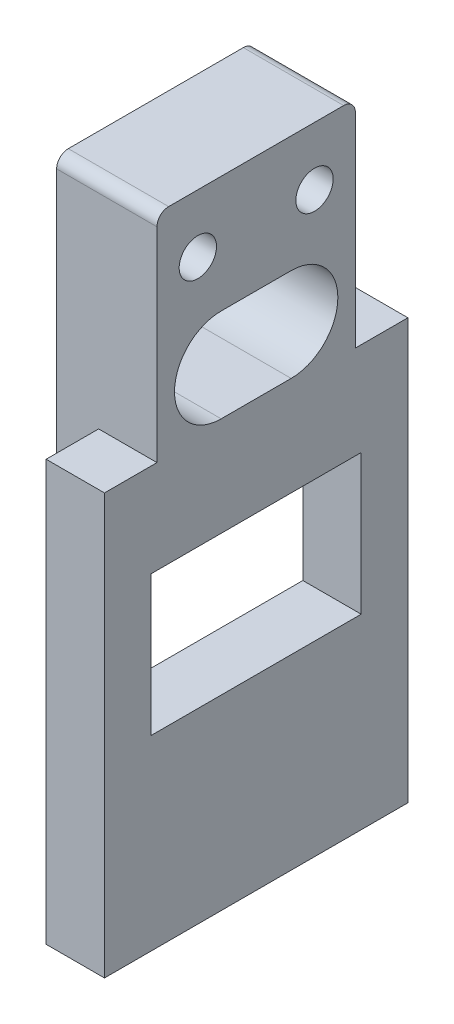
SolidWorks part; units mm, degrees
note: The reader was unsure of these and kept them because the rebuilt part matched: shared geometry of "Sketch2<3>", "Sketch2<7>".
material "ABS"
ref_plane "Front Plane" through (0, 0, 0) normal (0, 0, 1) x (1, 0, 0)
ref_plane "Top Plane" through (0, 0, 0) normal (0, 1, 0) x (1, 0, 0)
ref_plane "Right Plane" through (0, 0, 0) normal (1, 0, 0) x (0, 0, -1)
sketch "Sketch2" plane through (0, 0, 0) normal (1, 0, 0) x (0, 0, -1)
  line L0 (9, 19.5) -> (-9, 19.5) construction
  line L1 (-9, 19.5) -> (-9, 7.5) construction
  line L2 (9, 7.5) -> (-9, 7.5) construction
  line L3 (9, 19.5) -> (9, 7.5) construction
  line L4 (-11, 20.5) -> (11, 20.5) construction
  line L5 (11, 20.5) -> (11, -7.5) construction
  line L6 (11, -7.5) -> (-11, -7.5) construction
  line L7 (-11, -7.5) -> (-11, 20.5) construction
  line L8 (-3, 28) -> (3, 28) construction
  line L9 (-3, 36) -> (3, 36) construction
  line L10 (8.5, 22.5) -> (-8.5, 22.5) construction
  line L11 (8.5, 27.5) -> (-8.5, 27.5) construction
  line L12 (8.5, 46) -> (8.5, 22.5) construction
  line L13 (8.5, 22.5) -> (13, 22.5) construction
  line L14 (13, 22.5) -> (13, -8.5) construction
  line L15 (13, -8.5) -> (-13, -8.5) construction
  line L16 (-13, -8.5) -> (-13, 22.5) construction
  line L17 (-13, 22.5) -> (-8.5, 22.5) construction
  line L18 (-8.5, 22.5) -> (-8.5, 46) construction
  line L19 (-8.5, 46) -> (8.5, 46) construction
  line L20 (9, 19.5) -> (-9, 19.5)
  line L21 (-9, 19.5) -> (-9, 7.5)
  line L22 (9, 7.5) -> (-9, 7.5)
  line L23 (9, 19.5) -> (9, 7.5)
  line L24 (-11, 20.5) -> (11, 20.5)
  line L25 (11, 20.5) -> (11, -7.5)
  line L26 (11, -7.5) -> (-11, -7.5)
  line L27 (-11, -7.5) -> (-11, 20.5)
  line L28 (-3, 28) -> (3, 28)
  line L29 (-3, 36) -> (3, 36)
  line L30 (8.5, 22.5) -> (-8.5, 22.5)
  line L31 (8.5, 27.5) -> (-8.5, 27.5)
  line L32 (8.5, 46) -> (8.5, 22.5)
  line L33 (8.5, 22.5) -> (13, 22.5)
  line L34 (13, 22.5) -> (13, -8.5)
  line L35 (13, -8.5) -> (-13, -8.5)
  line L36 (-13, -8.5) -> (-13, 22.5)
  line L37 (-13, 22.5) -> (-8.5, 22.5)
  line L38 (-8.5, 22.5) -> (-8.5, 46)
  line L39 (-8.5, 46) -> (8.5, 46)
  line L40 (-13, 27.5) -> (-13, 22.5) construction
  line L41 (-8.5, 27.5) -> (-13, 27.5) construction
  line L42 (13, 22.5) -> (13, 27.5) construction
  line L43 (13, 27.5) -> (8.5, 27.5) construction
  line L44 (-13, 27.5) -> (-13, 22.5)
  line L45 (-8.5, 27.5) -> (-13, 27.5)
  line L46 (13, 22.5) -> (13, 27.5)
  line L47 (13, 27.5) -> (8.5, 27.5)
  arc A0 (3, 28) -> (3, 36) centre (3, 32) ccw construction
  arc A1 (-3, 36) -> (-3, 28) centre (-3, 32) ccw construction
  arc A2 (3, 28) -> (3, 36) centre (3, 32) ccw
  arc A3 (-3, 36) -> (-3, 28) centre (-3, 32) ccw
extrude "Boss-Extrude1" add sketch "Sketch2" against normal up to vertex from vertex contours L37 L36 L35 L34 L33 L30 L26 L27 L24 L25 | L27 L26 L25 L24 L20 L23 L22 L21 | L46 L47 L32 L33 | L38 L30 L32 L31 | L38 L45 L44 L37
extrude "Boss-Extrude2" add sketch "Sketch2<3>" along normal up to vertex (8.6 mm away) contours L38 L30 L32 L31
sketch "Sketch2<3>" plane through (0, 0, 0) normal (1, 0, 0) x (0, 0, -1) same geometry as "Sketch2"
extrude "Boss-Extrude3" add sketch "Sketch2<7>" along normal up to vertex (8.6 mm away) contours L39 L38 L31 L32 A3 L29 A2 L28
sketch "Sketch2<7>" plane through (0, 0, 0) normal (1, 0, 0) x (0, 0, -1) same geometry as "Sketch2"
hole_wizard "M3 Clearance Hole1" positions "Sketch3" profile "Sketch4" hole size "M3" standard "ISO"
sketch "Sketch3" plane through (8.6, 0, 0) normal (1, 0, 0) x (0, 0, -1)
  point P0 (-5, 41)
  point P2 (5, 41)
sketch "Sketch4" plane through (8.6, 41, 5) normal (0, 1, 0) x (0, 0, -1)
  line L0 (0, 0) -> (0, 5.9614)
  line L1 (0, 5.9614) -> (1.6, 5)
  line L2 (1.6, 5) -> (1.6, 0)
  line L5 (1.6, 0) -> (0, 0)
  line L10 (0, 5.9614) -> (-1.6, 5) construction
  line L11 (0, -6.35) -> (0, 107.95) construction
  dimension "Hole Dia." = 3.2
  dimension "Hole Depth" = 5
  dimension "Drill Angle" = 118
fillet "Fillet1" radius 1 4 edges at (4.3, 46, -8.5) (1.8, 22.5, -8.5) (1.8, 22.5, 8.5) (4.3, 46, 8.5)
